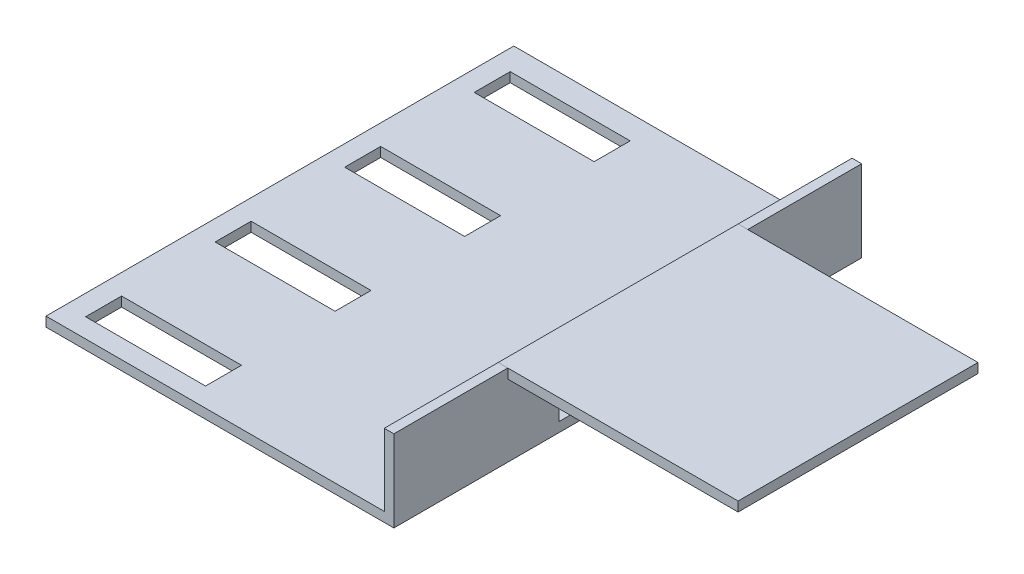
SolidWorks part; units mm, degrees
ref_plane "Front Plane" through (0, 0, 0) normal (0, 0, 1) x (1, 0, 0)
ref_plane "Top Plane" through (0, 0, 0) normal (0, 1, 0) x (1, 0, 0)
ref_plane "Right Plane" through (0, 0, 0) normal (1, 0, 0) x (0, 0, -1)
sketch "Sketch1" plane through (0, 0, 0) normal (0, 1, 0) x (1, 0, 0)
  line L1 (-29, -39) -> (29, -39)
  line L2 (-29, -39) -> (-29, 39)
  line L3 (-29, 39) -> (29, 39)
  line L4 (29, -39) -> (29, 39)
  line L5 (-29, -39) -> (29, 39) construction
  line L6 (-29, 39) -> (29, -39) construction
  point P0 (0, 0)
  dimension "D1" = 58
  dimension "D2" = 78
extrude "Boss-Extrude1" add sketch "Sketch1" along normal blind 1.6
sketch "Sketch2" plane through (0, 1.6, 0) normal (0, 1, 0) x (1, 0, 0)
  line L0 (-29, -39) -> (29, -39) construction
  line L1 (29, 39) -> (27.4, 39)
  line L2 (29, 39) -> (29, -39)
  line L3 (29, -39) -> (27.4, -39)
  line L4 (27.4, 39) -> (27.4, -39)
  dimension "D1" = 1.6
extrude "Boss-Extrude2" add sketch "Sketch2" along normal blind 12
ref_plane "Plane1" through (27.4, 13.6, -39) normal (0, 0, 1) x (1, 0, 0)
sketch "Sketch3" plane through (35.9, 13.6, -42.5) normal (0, -1, 0) x (1, 0, 0)
  line L0 (19.1, 42.5) -> (-90.9, 42.5) construction
  line L1 (-8.5, 22.5) -> (31.5, 22.5)
  line L2 (-8.5, 22.5) -> (-8.5, 62.5)
  line L3 (-8.5, 62.5) -> (31.5, 62.5)
  line L4 (31.5, 22.5) -> (31.5, 62.5)
  line L5 (-8.5, 3.5) -> (-8.5, 81.5) construction
  point P6 (-8.5, 42.5)
  dimension "D1" = 40
  dimension "D2" = 40
extrude "Boss-Extrude3" add sketch "Sketch3" along normal blind 1.6 separate body
sketch "Sketch4" plane through (27.4, 0, 0) normal (-1, 0, 0) x (0, 0, 1)
  line L0 (0, -55) -> (0, 55) construction
  line L1 (-11.5, 10.1) -> (11.5, 10.1)
  line L2 (-11.5, 10.1) -> (-11.5, 1.6)
  line L3 (-11.5, 1.6) -> (11.5, 1.6)
  line L4 (11.5, 10.1) -> (11.5, 1.6)
  line L5 (-11.5, 10.1) -> (11.5, 1.6) construction
  line L6 (-11.5, 1.6) -> (11.5, 10.1) construction
  line L8 (-39, 1.6) -> (39, 1.6) construction
  point P0 (0, 5.85)
  dimension "D1" = 8.5
  dimension "D2" = 23
extrude "Cut-Extrude1" cut sketch "Sketch4" against normal blind 1.6
sketch "Sketch5" plane through (0, 1.6, 0) normal (0, 1, 0) x (1, 0, 0)
  line L1 (-25.6, 29) -> (-5.6, 29)
  line L2 (-25.6, 29) -> (-25.6, 35)
  line L3 (-25.6, 35) -> (-5.6, 35)
  line L4 (-5.6, 29) -> (-5.6, 35)
  line L6 (-7.48, 0) -> (7.48, 0) construction
  line L7 (27.4, 39) -> (27.4, 11.5) construction
  point P13 (0, 0)
  point P14 (0, 0)
  point P15 (-26.1289, 24.2289)
  dimension "D1" = 20
  dimension "D2" = 6
  dimension "D3" = 29
  dimension "D4" = 33
extrude "Cut-Extrude2" cut sketch "Sketch5" against normal blind 1.6
pattern_linear "LPattern1" count 4 spacing 21.6 along (0, 0, 1) of "Cut-Extrude2"
